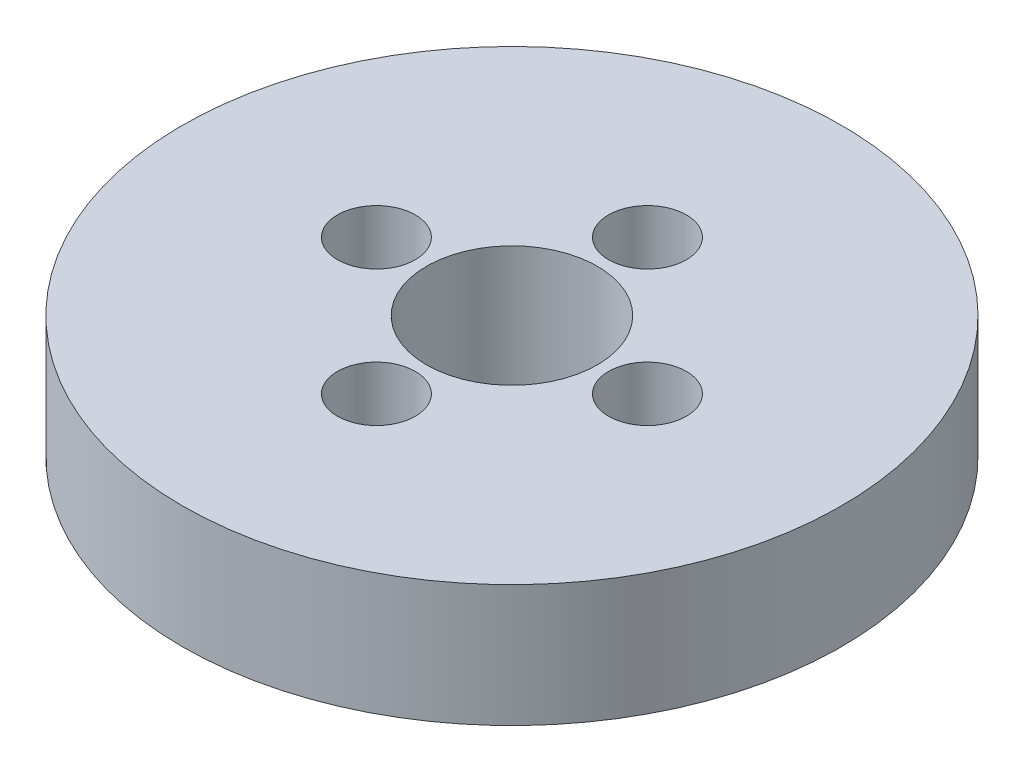
SolidWorks part; units mm, degrees
ref_plane "Front Plane" through (0, 0, 0) normal (0, 0, 1) x (1, 0, 0)
ref_plane "Top Plane" through (0, 0, 0) normal (0, 1, 0) x (1, 0, 0)
ref_plane "Right Plane" through (0, 0, 0) normal (1, 0, 0) x (0, 0, -1)
sketch "Sketch1" plane through (0, 0, 0) normal (0, 1, 0) x (1, 0, 0)
  circle A0 centre (0, 0) radius 67.5
  dimension "FLANGE_OD" = 135
extrude "Boss-Extrude1" add sketch "Sketch1" along normal blind 25
sketch "Sketch2" plane through (0, 0, 0) normal (0, 1, 0) x (1, 0, 0)
  circle A0 centre (0, 0) radius 17.5
  dimension "BORE_D" = 35
extrude "Cut-Extrude1" cut sketch "Sketch2" along normal through all
sketch "Sketch3" plane through (0, 25, 0) normal (0, 1, 0) x (1, 0, 0)
  circle A0 centre (0, 0) radius 27.7595 construction
  circle A1 centre (-27.7595, 0) radius 7.9696
  dimension "BOLT_D" = 15.9391
  dimension "BOLT_PCD" = 55.519
extrude "Cut-Extrude2" cut sketch "Sketch3" against normal blind 21.2759
pattern_circular "CirPattern1" count 4 over 360 about axis through (0, 0, 0) along (0, 1, 0) of "Cut-Extrude2"
